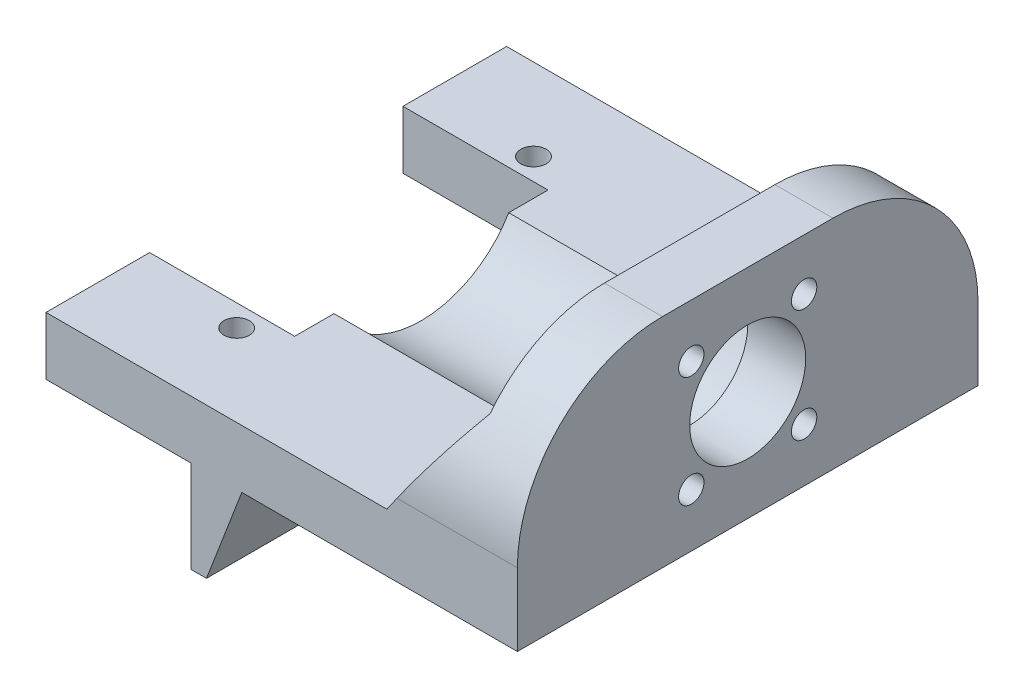
SolidWorks part; units mm, degrees
ref_plane "Front Plane" through (0, 0, 0) normal (0, 0, 1) x (1, 0, 0)
ref_plane "Top Plane" through (0, 0, 0) normal (0, 1, 0) x (1, 0, 0)
ref_plane "Right Plane" through (0, 0, 0) normal (1, 0, 0) x (0, 0, -1)
sketch "Sketch1" plane through (0, 0, 0) normal (0, 1, 0) x (1, 0, 0)
  line L0 (0, -17.465) -> (0, 17.465)
  line L1 (0, -55) -> (0, 55) construction
  line L2 (0, 17.465) -> (-20, 17.465)
  line L3 (-20, 17.465) -> (-20, 31.755)
  line L4 (-20, 31.755) -> (45, 31.755)
  line L5 (45, 31.755) -> (45, -31.755)
  line L6 (-55, 0) -> (55, 0) construction
  line L7 (45, 0) -> (0, 0)
  line L8 (-20, -31.755) -> (45, -31.755)
  line L9 (-20, -17.465) -> (-20, -31.755)
  line L10 (0, -17.465) -> (-20, -17.465)
  dimension "D1" = 20
  dimension "D2" = 31.755
  dimension "D3" = 17.465
  dimension "D4" = 65
extrude "Boss-Extrude1" add sketch "Sketch1" along normal blind 30 contours L0 L10 L9 L8 L5 L7 | L7 L5 L4 L3 L2 L0 region at (17.0833, 0, 17.3329) region at (17.0833, 0, -17.3329)
sketch "Sketch2" plane through (0, 0, 31.755) normal (0, 0, 1) x (1, 0, 0)
  line L0 (55, 0) -> (-55, 0) construction
  line L1 (-20, 30) -> (37, 30)
  line L2 (-20, 30) -> (-20, 8)
  line L3 (-20, 8) -> (37, 8)
  line L4 (37, 30) -> (37, 8)
  line L5 (45, 30) -> (45, 0) construction
  dimension "D1" = 8
  dimension "D2" = 8
extrude "Cut-Extrude1" cut sketch "Sketch2" against normal through all
sketch "Sketch4" plane through (45, 0, 0) normal (1, 0, 0) x (0, 0, -1)
  line L0 (0, 55) -> (0, -55) construction
  line L1 (55, 0) -> (-55, 0) construction
  line L3 (-7.7782, 7.3568) -> (7.7782, 7.3568) construction
  line L4 (-7.7782, 7.3568) -> (-7.7782, 22.9132) construction
  line L5 (-7.7782, 22.9132) -> (7.7782, 22.9132) construction
  line L6 (7.7782, 7.3568) -> (7.7782, 22.9132) construction
  line L7 (-7.7782, 7.3568) -> (7.7782, 22.9132) construction
  line L8 (-7.7782, 22.9132) -> (7.7782, 7.3568) construction
  circle A0 centre (0, 15.135) radius 8
  circle A1 centre (0, 15.135) radius 11 construction
  circle A2 centre (-7.7782, 22.6833) radius 1.75
  circle A3 centre (7.7782, 22.9132) radius 1.75
  circle A4 centre (7.7782, 7.3568) radius 1.75
  circle A5 centre (-7.7782, 7.3568) radius 1.75
  dimension "D1" = 16
  dimension "D2" = 15.135
  dimension "D3" = 22
  dimension "D4" = 3.5
extrude "Cut-Extrude2" cut sketch "Sketch4" against normal through all
sketch "Sketch5" plane through (0, 0, 0) normal (-1, 0, 0) x (0, 0, 1)
  circle A0 centre (0, 15.135) radius 14
  dimension "D1" = 28
extrude "Cut-Extrude3" cut sketch "Sketch5" against normal up to surface (37 mm away) up to face at (37, 24.6632, -7.7782)
sketch "Sketch6" plane through (0, 8, 0) normal (0, 1, 0) x (1, 0, 0)
  line L0 (-20, -17.465) -> (0, -17.465) construction
  line L2 (0, -12.0454) -> (0, -17.465) construction
  circle A0 centre (-5, -20.465) radius 1.75
  dimension "D1" = 3.5
  dimension "D3" = 5
  dimension "D2" = 3
extrude "Cut-Extrude4" cut sketch "Sketch6" against normal through all
mirror "Mirror1" about plane through (0, 0, 0) normal (0, 0, 1) of "Cut-Extrude4"
sketch "Sketch7" plane through (45, 0, 0) normal (1, 0, 0) x (0, 0, -1)
  line L0 (15, 15.135) -> (18, 15.135)
  line L1 (18, 15.135) -> (18, 0)
  line L2 (55, 0) -> (-55, 0) construction
  line L3 (18, 0) -> (-18, 0)
  line L4 (-18, 0) -> (-18, 15.135)
  line L5 (-18, 15.135) -> (-15, 15.135)
  arc A2 (-15, 15.135) -> (0, 0.135) centre (0, 15.135) ccw
  arc A3 (-15, 15.135) -> (0, 0.135) centre (0, 15.135) ccw
  arc A4 (0, 0.135) -> (15, 15.135) centre (0, 15.135) ccw
ref_plane "Plane1" through (37, 8, 31.755) normal (0, 0, 1) x (1, 0, 0)
chamfer "Chamfer1" distance 10 angle 55 2 edges at (37, 8, -21.9002) (37, 8, 21.9002) first distance on face at (-5, 8, -22.215) first distance on face at (-5, 8, 22.215)
fillet "Fillet3" radius 20 2 edges at (41, 30, -31.755) (41, 30, 31.755)
sketch "Sketch11" plane through (0, 0, 0) normal (0, -1, 0) x (1, 0, 0)
  line L0 (92, 31.755) -> (-18, 31.755) construction
  line L1 (0, 17.465) -> (2, 17.465)
  line L2 (0, 17.465) -> (0, 31.755)
  line L3 (0, 31.755) -> (2, 31.755)
  line L4 (2, 17.465) -> (2, 31.755)
  line L5 (-20, -31.755) -> (45, -31.755) construction
  line L6 (0, -17.465) -> (2, -17.465)
  line L7 (0, -17.465) -> (0, -31.755)
  line L8 (0, -31.755) -> (2, -31.755)
  line L9 (2, -17.465) -> (2, -31.755)
  line L10 (0, 17.465) -> (0, -17.465) construction
  line L11 (0, 7.145) -> (2, 7.145)
  line L12 (0, 7.145) -> (0, -7.145)
  line L13 (0, -7.145) -> (2, -7.145)
  line L14 (2, 7.145) -> (2, -7.145)
  dimension "D1" = 2
extrude "Boss-Extrude3" add sketch "Sketch11" along normal blind 12.7
chamfer "Chamfer2" distance 5 angle 69 3 edges at (2, 0, 0) (2, 0, -24.61) first distance on face at (6.7083, 0, -0.5954)
